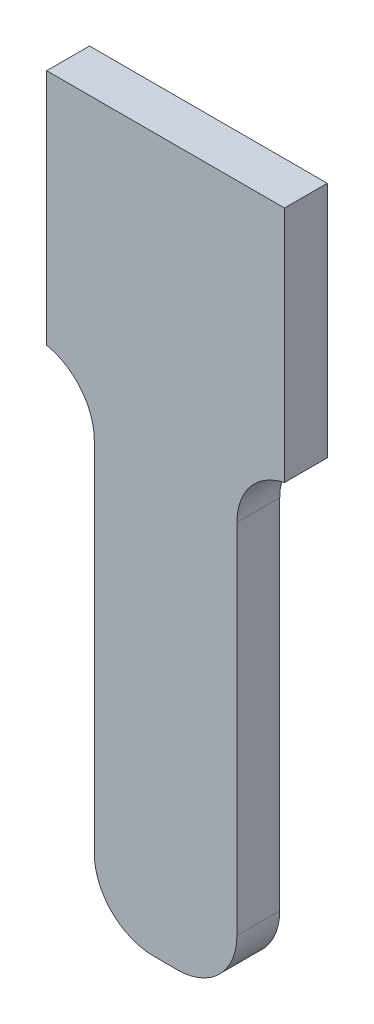
SolidWorks part; units mm, degrees
material "Custom Plastic"
ref_plane "X-Y Datum" through (0, 0, 0) normal (0, 0, 1) x (1, 0, 0)
ref_plane "X-Z Datum" through (0, 0, 0) normal (0, 1, 0) x (1, 0, 0)
ref_plane "Y-Z Datum" through (0, 0, 0) normal (1, 0, 0) x (0, 0, -1)
sketch "Sketch1" plane through (0, 0, 0) normal (0, 0, 1) x (1, 0, 0)
  line L0 (0, -31.75) -> (0, -6.35) construction
  line L1 (-6.35, 6.35) -> (6.35, 6.35)
  line L2 (-6.35, 6.35) -> (-6.35, -6.35)
  line L3 (-6.35, -6.35) -> (6.35, -6.35)
  line L4 (6.35, 6.35) -> (6.35, -6.35)
  line L5 (-6.35, 6.35) -> (6.35, -6.35) construction
  line L6 (-6.35, -6.35) -> (6.35, 6.35) construction
  line L7 (-3.81, -6.35) -> (3.81, -6.35)
  line L8 (-3.81, -6.35) -> (-3.81, -31.75)
  line L9 (-3.81, -31.75) -> (3.81, -31.75)
  line L10 (3.81, -6.35) -> (3.81, -31.75)
  point P0 (0, 0)
  dimension "D1" = 12.7
  dimension "D2" = 12.7
  dimension "D3" = 25.4
  dimension "D4" = 7.62
extrude "Boss-Extrude1" add sketch "Sketch1" along normal blind 2.286 contours L10 L3 L8 L9 | L4 L1 L2 L3 region at (0, 0, 0) region at (0, -19.05, 0)
fillet "Fillet1" radius 3.175 4 edges at (-3.81, -6.35, 1.143) (3.81, -6.35, 1.143) (-3.81, -31.75, 1.143) (3.81, -31.75, 1.143)
